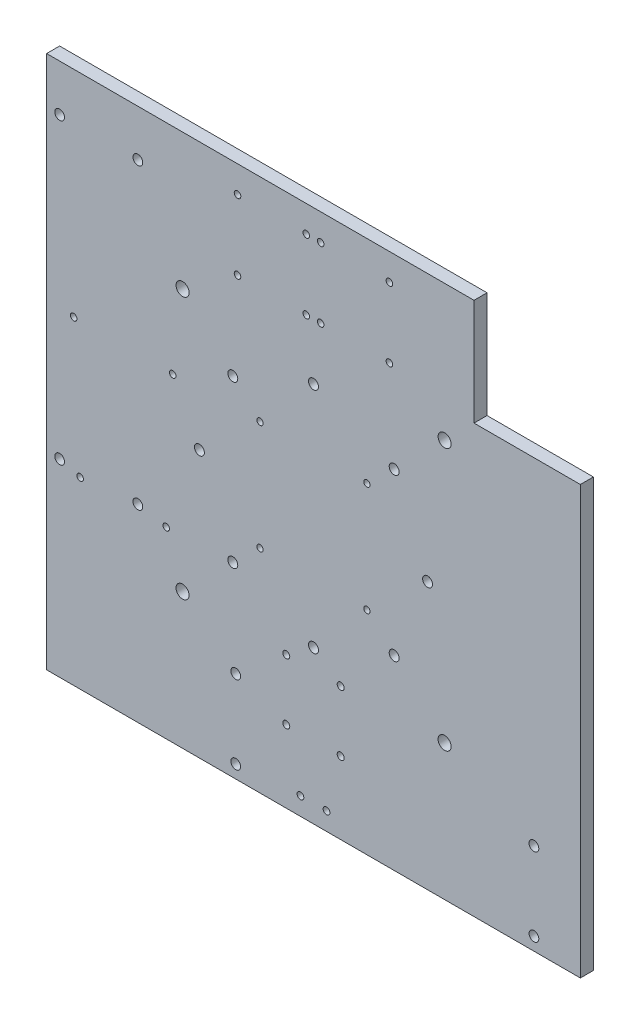
SolidWorks part; units mm, degrees
material "Perspex (TM) GS Acrylic Cast Sheet"
ref_plane "Front Plane" through (0, 0, 0) normal (0, 0, 1) x (1, 0, 0)
ref_plane "Top Plane" through (0, 0, 0) normal (0, 1, 0) x (1, 0, 0)
ref_plane "Right Plane" through (0, 0, 0) normal (1, 0, 0) x (0, 0, -1)
sketch "Sketch1" plane through (0, 0, 0) normal (0, 0, 1) x (1, 0, 0)
  line L0 (-130, 130) -> (130, 130)
  line L1 (130, 130) -> (130, -130)
  line L2 (130, -130) -> (-130, -130)
  line L3 (-130, -130) -> (-130, 130)
  line L4 (-120, 33.6598) -> (-120, -33.6505)
  line L5 (-29, 8) -> (-29, -8)
  line L6 (-29, 8) -> (-26.035, 8)
  line L7 (-26.035, 8) -> (-26.035, -8)
  line L8 (32.385, 33.02) -> (-32.385, 33.02)
  line L9 (-26.035, -8) -> (-29, -8)
  line L10 (-32.385, 33.02) -> (-32.385, -33.02)
  line L11 (-32.385, -33.02) -> (32.385, -33.02)
  line L12 (32.385, -33.02) -> (32.385, 33.02)
  line L13 (-107.2982, -46.3523) -> (-77.9253, -46.3523)
  line L14 (-113.65, 40.0098) -> (-71.5759, 40.0098)
  line L15 (-79.4148, 40.0098) -> (-79.4148, 22.9992)
  line L16 (-65.2259, -33.6529) -> (-65.2259, 33.6598)
  line L17 (-79.4148, 22.9992) -> (-94.8974, 22.9992)
  line L18 (-40, 120) -> (40, 120)
  line L19 (-94.8974, 22.9992) -> (-94.8974, 40.0098)
  line L31 (-40, 120) -> (-40, 80)
  line L32 (-40, 80) -> (40, 80)
  line L33 (40, 80) -> (40, 120)
  line L34 (-35, 100) -> (-35, 114.5)
  line L35 (-35, 114.5) -> (-29, 114.5)
  line L36 (-29, 114.5) -> (-29, 85.5)
  line L37 (-29, 85.5) -> (-35, 85.5)
  line L38 (-35, 85.5) -> (-35, 100)
  line L46 (16.75, -63) -> (16.75, -97)
  line L49 (16.75, -97) -> (-16.75, -97)
  line L50 (-16.75, -97) -> (-16.75, -63)
  line L51 (-16.75, -63) -> (16.75, -63)
  line L56 (120, 41.2) -> (120, -41.2)
  line L57 (45, 41.2) -> (45, -41.2)
  line L58 (120, 41.2) -> (45, 41.2)
  line L60 (45, -41.2) -> (120, -41.2)
  circle A0 centre (-26.035, 26.67) radius 1.55
  circle A1 centre (-26.035, -26.67) radius 1.55
  circle A2 centre (26.035, 26.67) radius 1.55
  circle A3 centre (26.035, -26.67) radius 1.55
  circle A4 centre (-116.825, 25.4027) radius 1.5875
  circle A5 centre (-113.65, -40.6352) radius 1.5875
  arc A6 (-120, -33.6505) -> (-107.2982, -46.3523) centre (-107.2982, -33.6505) ccw
  arc A7 (-77.9253, -46.3523) -> (-65.2259, -33.6529) centre (-77.9253, -33.6529) ccw
  arc A8 (-113.65, 40.0098) -> (-120, 33.6598) centre (-113.65, 33.6598) ccw
  arc A9 (-65.2259, 33.6598) -> (-71.5759, 40.0098) centre (-71.5759, 33.6598) ccw
  circle A10 centre (-68.565, 25.4048) radius 1.5875
  circle A11 centre (-37, 117) radius 1.6
  circle A12 centre (-37, 83) radius 1.6
  circle A13 centre (-3.5, 117) radius 1.6
  circle A14 centre (-3.5, 83) radius 1.6
  circle A15 centre (3.5, 117) radius 1.6
  circle A16 centre (37, 117) radius 1.6
  circle A17 centre (37, 83) radius 1.6
  circle A18 centre (3.5, 83) radius 1.6
  circle A19 centre (-13.25, -65.25) radius 1.7
  circle A20 centre (13.25, -65.25) radius 1.7
  circle A21 centre (13.25, -94.75) radius 1.7
  circle A22 centre (-13.25, -94.75) radius 1.7
  circle A23 centre (-76.33, 76.33) radius 3.175
  circle A24 centre (0, 55.575) radius 2.415
  circle A25 centre (-55.575, 0) radius 2.415
  circle A26 centre (0, -55.575) radius 2.415
  circle A27 centre (55.575, 0) radius 2.415
  circle A28 centre (-39.2975, 39.2975) radius 2.415
  circle A29 centre (39.2975, 39.2975) radius 2.415
  circle A30 centre (39.2975, -39.2975) radius 2.415
  circle A31 centre (-39.2975, -39.2975) radius 2.415
  circle A32 centre (76.33, 76.33) radius 3.175
  circle A33 centre (76.33, -76.33) radius 3.175
  circle A34 centre (-76.33, -76.33) radius 3.175
  arc A35 (-2.4144, 55.5225) -> (-37.5531, 40.9676) centre (0, 0) ccw
  arc A36 (37.5531, 40.9676) -> (2.4144, 55.5225) centre (0, 0) ccw
  arc A37 (55.5225, 2.4144) -> (40.9676, 37.5531) centre (0, 0) ccw
  arc A38 (40.9676, -37.5531) -> (55.5225, -2.4144) centre (0, 0) ccw
  arc A39 (2.4144, -55.5225) -> (37.5531, -40.9676) centre (0, 0) ccw
  arc A40 (-37.5531, -40.9676) -> (-2.4144, -55.5225) centre (0, 0) ccw
  arc A41 (-55.5225, -2.4144) -> (-40.9676, -37.5531) centre (0, 0) ccw
  arc A42 (-40.9676, 37.5531) -> (-55.5225, 2.4144) centre (0, 0) ccw
  circle A43 centre (-71.74, -40.6352) radius 1.5875
  circle A44 centre (6.35, -121.3) radius 1.651
  circle A45 centre (-6.35, -121.3) radius 1.651
  circle A46 centre (121.3, 126.35) radius 1.651
  circle A47 centre (121.3, 113.65) radius 1.651
  point P127 (127.65, 120)
  point P128 (-120, -120)
  point P129 (0, -127.65)
extrude "Boss-Extrude2" add sketch "Sketch1" along normal blind 6.35 contours L0 L1 L2 L3 | A10 | A43 | A5 | A4 | A25 | A28 | A24 | A31 | A26 | A30 | A27 | A29 | A1 | A3 | A2 | A0 | A22 | A21 | A20 | A19 | A45 | A44 | A46 | A47 | A17 | A16 | A18 | A14 | A15 | A13 | A11 | A12
sketch "Sketch2" plane through (0, 0, 0) normal (0, 0, -1) x (-1, 0, 0)
  circle A0 centre (0, 0) radius 55.6086 construction
sketch "Sketch5" plane through (0, 0, 0) normal (0, 0, -1) x (-1, 0, 0)
  line L0 (-78.2, 78.2) -> (-78.2, 131)
  line L1 (-78.2, 131) -> (-131, 131)
  line L2 (-131, 131) -> (-131, 78.2)
  line L3 (-131, 78.2) -> (-78.2, 78.2)
  line L4 (-130, 130) -> (-130, 79.2)
  line L5 (-130, 79.2) -> (-79.2, 79.2)
  line L6 (-79.2, 79.2) -> (-79.2, 130)
  line L7 (-79.2, 130) -> (-130, 130)
  line L8 (-130, 130) -> (-130, 79.2)
  line L9 (-130, 79.2) -> (-79.2, 79.2)
  line L10 (-79.2, 79.2) -> (-79.2, 130)
  line L11 (-79.2, 130) -> (-130, 130)
  dimension "D1" = 0
  dimension "D2" = 1
extrude "Cut-Extrude1" cut sketch "Sketch5" against normal through all contours L2 L3 L0 L1
sketch "Sketch6" plane through (0, 0, 0) normal (0, 0, -1) x (-1, 0, 0)
  circle A0 centre (63.7786, 63.7786) radius 3.175 construction
  circle A1 centre (-63.8746, 63.7786) radius 3.175 construction
  circle A2 centre (-63.8746, -63.8746) radius 3.175 construction
  circle A3 centre (63.7786, -63.8746) radius 3.175 construction
  circle A4 centre (63.7786, 63.7786) radius 3.175
  circle A5 centre (-63.8746, 63.7786) radius 3.175
  circle A6 centre (-63.8746, -63.8746) radius 3.175
  circle A7 centre (63.7786, -63.8746) radius 3.175
extrude "Cut-Extrude2" cut sketch "Sketch6" against normal through all contours A7 | A6 | A5 | A4
sketch "Sketch7" plane through (0, 0, 0) normal (0, 0, -1) x (-1, 0, 0)
  circle A0 centre (123.65, -37.8781) radius 2.3812 construction
  circle A1 centre (85.55, -37.8781) radius 2.3812
  circle A2 centre (85.55, -37.8781) radius 2.3812
  circle A3 centre (123.65, 107.3781) radius 2.3813 construction
  circle A4 centre (123.65, -37.8781) radius 2.3813
  circle A5 centre (123.65, 107.3781) radius 2.3813
  circle A6 centre (85.55, 107.3781) radius 2.3813 construction
  circle A7 centre (85.55, 107.3781) radius 2.3813
  circle A8 centre (37.8781, -123.65) radius 2.3812 construction
  circle A9 centre (37.8781, -85.55) radius 2.3812 construction
  circle A10 centre (-107.3781, -123.65) radius 2.3812 construction
  circle A11 centre (-107.3781, -85.55) radius 2.3812 construction
  circle A12 centre (37.8781, -123.65) radius 2.3812
  circle A13 centre (37.8781, -85.55) radius 2.3812
  circle A14 centre (-107.3781, -123.65) radius 2.3812
  circle A15 centre (-107.3781, -85.55) radius 2.3812
  dimension "D1" = 0
extrude "Cut-Extrude3" cut sketch "Sketch7" against normal through all
